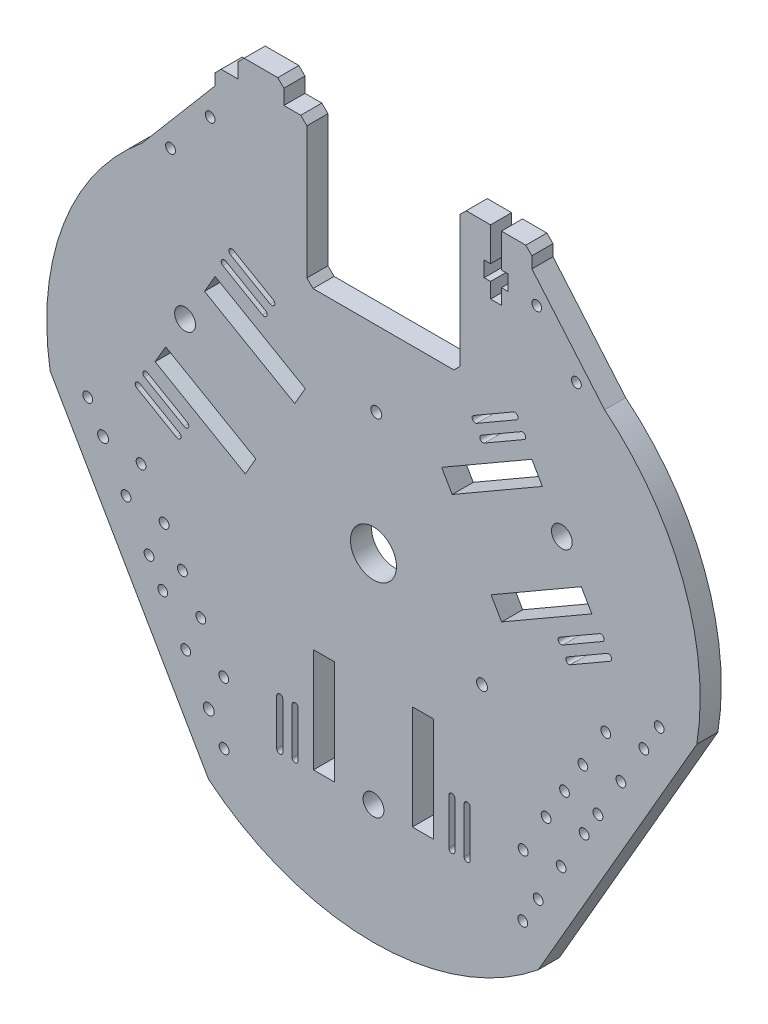
SolidWorks part; units mm, degrees
ref_plane "Front Plane" through (0, 0, 0) normal (0, 0, 1) x (1, 0, 0)
ref_plane "Top Plane" through (0, 0, 0) normal (0, 1, 0) x (1, 0, 0)
ref_plane "Right Plane" through (0, 0, 0) normal (1, 0, 0) x (0, 0, -1)
sketch "Sketch1" plane through (0, 0, 0) normal (0, 0, 1) x (1, 0, 0)
  circle A0 centre (0, 0) radius 110
  dimension "D1" = 220
extrude "Boss-Extrude1" add sketch "Sketch1" along normal blind 6.88
sketch "Sketch2" plane through (0, 0, 6.88) normal (0, 0, 1) x (1, 0, 0)
  line L0 (-105.5392, -1.2008) -> (-53.8095, -90.7992)
  line L1 (53.8095, -90.7992) -> (105.5392, -1.2008)
  line L2 (51.7297, 92) -> (-51.7297, 92)
  line L3 (-21.6506, 12.5) -> (21.6506, 12.5)
  line L4 (21.6506, 12.5) -> (0, -25)
  line L5 (0, -25) -> (-21.6506, 12.5)
  line L6 (0, 12.5) -> (0, 0) construction
  line L7 (0, 0) -> (-10.8253, -6.25) construction
  line L8 (10.8253, -6.25) -> (0, 0) construction
  arc A0 (-53.8095, -90.7992) -> (53.8095, -90.7992) centre (0, -25) ccw
  arc A1 (105.5392, -1.2008) -> (51.7297, 92) centre (21.6506, 12.5) ccw
  arc A2 (-51.7297, 92) -> (-105.5392, -1.2008) centre (-21.6506, 12.5) ccw
  circle A3 centre (0, 0) radius 250
  circle A4 centre (0, 0) radius 110
  circle M1 centre (0, 0) radius 110
  dimension "D3" = 220
  dimension "D4" = 500
  dimension "D5" = 85
  dimension "D1" = 92
extrude "Cut-Extrude1" cut sketch "Sketch2" against normal through all contours A3 M1 | A2 L2 A1 M1 | A2 A0 L0 M1 | A1 L1 A0 M1 region at (-84.8334, -48.9786, 6.88) region at (0, 97.9571, 6.88) region at (84.8334, -48.9786, 6.88) region at (-242.9289, 0, 6.88)
sketch "Sketch3" plane through (0, 0, 6.88) normal (0, 0, 1) x (1, 0, 0)
  line L0 (0, 0) -> (-95.2628, 55) construction
  line L1 (0, 0) -> (95.2628, 55) construction
  line L2 (0, 0) -> (0, -110) construction
  arc A0 (-51.7297, 92) -> (-105.5392, -1.2008) centre (-21.6506, 12.5) ccw construction
  arc A1 (105.5392, -1.2008) -> (51.7297, 92) centre (21.6506, 12.5) ccw construction
  arc A2 (-53.8095, -90.7992) -> (53.8095, -90.7992) centre (0, -25) ccw construction
sketch "Sketch4" plane through (0, 0, 0) normal (0, 0, -1) x (-1, 0, 0)
  line L0 (41.8329, 1.5432) -> (38.3929, 7.5015) construction
  line L1 (25.6929, 29.4985) -> (22.2529, 35.4568) construction
  line L2 (55.1378, 46.4985) -> (51.6978, 52.4568) construction
  line L3 (71.2778, 18.5432) -> (67.8378, 24.5015) construction
  line L4 (41.8329, 1.5432) -> (38.3929, 7.5015)
  line L5 (25.6929, 29.4985) -> (22.2529, 35.4568)
  line L6 (55.1378, 46.4985) -> (51.6978, 52.4568)
  line L7 (71.2778, 18.5432) -> (67.8378, 24.5015)
  line L8 (71.2778, 18.5432) -> (41.8329, 1.5432)
  line L9 (38.3929, 7.5015) -> (67.8378, 24.5015)
  line L10 (55.1378, 46.4985) -> (25.6929, 29.4985)
  line L11 (22.2529, 35.4568) -> (51.6978, 52.4568)
  line L12 (67.8378, 24.5015) -> (55.1378, 46.4985) construction
  line L13 (38.3929, 7.5015) -> (25.6929, 29.4985) construction
  line L14 (61.4878, 35.5) -> (32.0429, 18.5) construction
  circle A0 centre (32.0429, 18.5) radius 3.4 construction
  circle A1 centre (61.4878, 35.5) radius 3.4
  dimension "D1" = 6.8
extrude "Cut-Extrude2" cut sketch "Sketch4" against normal blind 10
ref_axis "Axis1" through (0, 0, -0.344) along (0, 0, 1)
pattern_circular "CirPattern1" count 3 over 360 about axis through (0, 0, -0.344) along (0, 0, 1) of "Cut-Extrude2"
sketch "Sketch6" plane through (0, 0, 6.88) normal (0, 0, 1) x (1, 0, 0)
  line L0 (-21.7297, 112) -> (-21.7297, 97)
  line L1 (51.7297, 92) -> (-51.7297, 92)
  line L2 (51.7297, 92) -> (51.7297, 112)
  line L3 (51.7297, 112) -> (28.2703, 112)
  line L4 (-51.7297, 92) -> (-51.7297, 112)
  line L5 (-21.7297, 97) -> (28.2703, 97)
  line L6 (28.2703, 97) -> (28.2703, 112)
  line L7 (-21.7297, 112) -> (-51.7297, 112)
  dimension "D1" = 20
  dimension "D2" = 15
  dimension "D3" = 50
  dimension "D4" = 30
extrude "Boss-Extrude2" add sketch "Sketch6" against normal up to vertex (6.88 mm away) up to point (51.7297, 92, 0)
chamfer "Chamfer1" distance 21 angle 45 2 edges at (-51.7297, 92, 3.44) (51.7297, 92, 3.44) first distance on face at (-51.7297, 102, 3.44) first distance on face at (51.7297, 102, 3.44)
sketch "Sketch7" plane through (0, 0, 6.88) normal (0, 0, 1) x (1, 0, 0)
  line L0 (-21.7297, 112) -> (-51.7297, 112) construction
  line L1 (-21.7297, 97) -> (28.2703, 97)
  line L2 (-21.7297, 97) -> (-21.7297, 65)
  line L3 (-21.7297, 65) -> (28.2703, 65)
  line L4 (28.2703, 97) -> (28.2703, 65)
  line L5 (28.2703, 112) -> (28.2703, 97) construction
  dimension "D1" = 47
extrude "Cut-Extrude5" cut sketch "Sketch7" against normal through all
sketch "Sketch8" plane through (0, 0, 6.88) normal (0, 0, 1) x (1, 0, 0)
  line L0 (51.7297, 112) -> (28.2703, 112) construction
  line L5 (41.775, 133) -> (38.225, 133)
  line L6 (41.775, 133) -> (41.775, 91)
  line L7 (41.775, 91) -> (38.225, 91)
  line L8 (38.225, 133) -> (38.225, 91)
  line L9 (41.775, 133) -> (38.225, 91) construction
  line L10 (41.775, 91) -> (38.225, 133) construction
  line L12 (43.86, 96) -> (36.14, 96)
  line L13 (43.86, 96) -> (43.86, 101)
  line L14 (43.86, 101) -> (36.14, 101)
  line L15 (36.14, 96) -> (36.14, 101)
  line L16 (43.86, 96) -> (36.14, 101) construction
  line L17 (43.86, 101) -> (36.14, 96) construction
  point P0 (40, 112)
  point P7 (40, 98.5)
  dimension "D1" = 3.55
  dimension "D2" = 21
  dimension "D3" = 7.72
  dimension "D4" = 5
  dimension "D5" = 11
extrude "Cut-Extrude6" cut sketch "Sketch8" against normal blind 6.88 contours L13 L14 L6 L12 | L6 L12 L8 L7 | L6 L14 L8 L12 | L15 L12 L8 L14 | L14 L6 L8 region at (40, 117, 6.88) region at (42.8175, 98.5, 6.88) region at (40, 98.5, 6.88) region at (37.1825, 98.5, 6.88) region at (40, 93.5, 6.88)
sketch "Sketch9" plane through (0, 0, 6.88) normal (0, 0, 1) x (1, 0, 0)
  line L0 (-21.7297, 112) -> (-51.7297, 112) construction
  line L1 (-29.2297, 105.12) -> (-44.2297, 105.12)
  line L2 (-29.2297, 105.12) -> (-29.2297, 118.88)
  line L3 (-29.2297, 118.88) -> (-44.2297, 118.88)
  line L4 (-44.2297, 105.12) -> (-44.2297, 118.88)
  line L5 (-29.2297, 105.12) -> (-44.2297, 118.88) construction
  line L6 (-29.2297, 118.88) -> (-44.2297, 105.12) construction
  point P0 (-36.7297, 112)
  dimension "D1" = 15
  dimension "D2" = 6.88
extrude "Boss-Extrude3" add sketch "Sketch9" against normal up to vertex (6.88 mm away) up to point (-21.7297, 112, 0)
sketch "Sketch10" plane through (0, 0, 6.88) normal (0, 0, 1) x (1, 0, 0)
  line L2 (19.58, -109) -> (19.58, -71) construction
  line L4 (25.58, -71) -> (25.58, -56) construction
  line L5 (24.58, -71) -> (24.58, -56)
  line L6 (26.58, -71) -> (26.58, -56)
  line L7 (25.58, -63.5) -> (30.58, -63.5) construction
  line L8 (28.08, -63.5) -> (28.08, -58.2067) construction
  line L9 (19.58, -71) -> (19.58, -37) construction
  line L10 (30.58, -71) -> (30.58, -56) construction
  line L11 (31.58, -71) -> (31.58, -56)
  line L12 (29.58, -71) -> (29.58, -56)
  line L15 (-25.58, -71) -> (-25.58, -56) construction
  line L16 (-24.58, -71) -> (-24.58, -56)
  line L17 (-26.58, -71) -> (-26.58, -56)
  line L18 (-30.58, -71) -> (-30.58, -56) construction
  line L19 (-31.58, -71) -> (-31.58, -56)
  line L20 (-29.58, -71) -> (-29.58, -56)
  line L21 (-28.08, -63.5) -> (-28.08, -58.2067) construction
  line L22 (-25.58, -63.5) -> (-30.58, -63.5) construction
  arc A0 (24.58, -71) -> (26.58, -71) centre (25.58, -71) ccw
  arc A1 (26.58, -56) -> (24.58, -56) centre (25.58, -56) ccw
  arc A2 (31.58, -71) -> (29.58, -71) centre (30.58, -71) cw
  arc A3 (29.58, -56) -> (31.58, -56) centre (30.58, -56) cw
  arc A4 (-24.58, -71) -> (-26.58, -71) centre (-25.58, -71) cw
  arc A5 (-26.58, -56) -> (-24.58, -56) centre (-25.58, -56) cw
  arc A6 (-31.58, -71) -> (-29.58, -71) centre (-30.58, -71) ccw
  arc A7 (-29.58, -56) -> (-31.58, -56) centre (-30.58, -56) ccw
  point P6 (25.58, -63.5)
  point P21 (30.58, -63.5)
  point P30 (-25.58, -63.5)
  point P37 (-30.58, -63.5)
  dimension "D1" = 2
  dimension "D2" = 15
  dimension "D3" = 5
  dimension "D4" = 1.5
extrude "Cut-Extrude7" cut sketch "Sketch10" against normal blind 6.88
pattern_circular "CirPattern2" count 3 over 360 about axis through (0, 0, -0.344) along (0, 0, 1) of "Cut-Extrude7"
sketch "Sketch11" plane through (0, 0, 0) normal (0, 0, -1) x (-1, 0, 0)
  line L0 (-0.9365, 40.3779) -> (-35.4365, -19.3779) construction
  line L1 (-35.4365, -19.3779) -> (53.7641, -70.8779) construction
  line L2 (53.7641, -70.8779) -> (88.2641, -11.1221) construction
  line L3 (88.2641, -11.1221) -> (-0.9365, 40.3779) construction
  line L4 (71.0141, -41) -> (79.6743, -46) construction
  line L5 (105.5392, -1.2008) -> (53.8095, -90.7992) construction
  circle A4 centre (-0.9365, 40.3779) radius 1.775
  circle A5 centre (-35.4365, -19.3779) radius 1.775
  circle A6 centre (88.2641, -11.1221) radius 1.775
  circle A7 centre (53.7641, -70.8779) radius 1.775
  dimension "D4" = 3.55
  dimension "D1" = 69
  dimension "D2" = 103
  dimension "D3" = 10
extrude "Cut-Extrude8" cut sketch "Sketch11" against normal blind 10
chamfer "Chamfer2" distance 2 angle 45 8 edges at (28.2703, 65, 3.44) (-21.7297, 65, 3.44) (28.2703, 112, 3.44) (51.7297, 112, 3.44) (-51.7297, 112, 3.44) (-44.2297, 118.88, 3.44) (-29.2297, 118.88, 3.44) (-21.7297, 112, 3.44)
sketch "Sketch13" plane through (0, 0, 0) normal (0, 0, -1) x (-1, 0, 0)
  circle A0 centre (0, 0) radius 7.5
  dimension "D1" = 15
extrude "Cut-Extrude10" cut sketch "Sketch13" against normal blind 10
sketch "Sketch15" plane through (0, 0, 0) normal (0, 0, -1) x (-1, 0, 0)
  line L1 (0, 0) -> (0, -110) construction
  line L2 (-34.5, 82) -> (-19.5, 82) construction
  line L3 (-27, 82) -> (-27, 72) construction
  line L4 (0, 92) -> (0, 117.1571) construction
  line L5 (27, 82) -> (27, 72) construction
  line L6 (34.5, 82) -> (19.5, 82) construction
  line L7 (-34.5, 82) -> (-44.5, 82) construction
  circle A0 centre (-34.5, 82) radius 1.6 construction
  circle A1 centre (-27, 72) radius 1.6 construction
  circle A2 centre (-19.5, 82) radius 1.6 construction
  circle A3 centre (-4.5, 82) radius 1.6 construction
  circle A4 centre (-12, 72) radius 1.6 construction
  circle A5 centre (0, 82) radius 1.6 construction
  circle A6 centre (0, 72) radius 1.6 construction
  circle A7 centre (12, 72) radius 1.6 construction
  circle A8 centre (4.5, 82) radius 1.6 construction
  circle A9 centre (19.5, 82) radius 1.6 construction
  circle A10 centre (27, 72) radius 1.6 construction
  circle A11 centre (34.5, 82) radius 1.6 construction
  circle A34 centre (53.7641, -70.8779) radius 1.6
  circle A35 centre (48.8538, -59.3827) radius 1.6
  circle A36 centre (61.2641, -57.8875) radius 1.6
  circle A37 centre (56.3538, -46.3923) radius 1.6
  circle A38 centre (68.7641, -44.8971) radius 1.6
  circle A39 centre (62.3538, -36) radius 1.6
  circle A40 centre (73.2641, -37.1029) radius 1.6
  circle A41 centre (68.3538, -25.6077) radius 1.6
  circle A42 centre (80.7641, -24.1125) radius 1.6
  circle A43 centre (75.8538, -12.6173) radius 1.6
  circle A44 centre (88.2641, -11.1221) radius 1.6
  circle A45 centre (-88.2641, -11.1221) radius 1.6
  circle A46 centre (-75.8538, -12.6173) radius 1.6
  circle A47 centre (-80.7641, -24.1125) radius 1.6
  circle A48 centre (-68.3538, -25.6077) radius 1.6
  circle A49 centre (-73.2641, -37.1029) radius 1.6
  circle A50 centre (-62.3538, -36) radius 1.6
  circle A51 centre (-68.7641, -44.8971) radius 1.6
  circle A52 centre (-56.3538, -46.3923) radius 1.6
  circle A53 centre (-61.2641, -57.8875) radius 1.6
  circle A54 centre (-48.8538, -59.3827) radius 1.6
  circle A55 centre (-53.7641, -70.8779) radius 1.6
  circle A56 centre (-44.5, 82) radius 1.6 construction
  circle A57 centre (44.5, 82) radius 1.6 construction
  circle A58 centre (93.2641, -2.4619) radius 1.6
  circle A59 centre (48.7641, -79.5381) radius 1.6
  circle A60 centre (-48.7641, -79.5381) radius 1.6
  circle A61 centre (-93.2641, -2.4619) radius 1.6
  point P78 (0, 0)
  point P80 (0, 0)
  point P92 (0, 0)
  dimension "D2" = 3.2
  dimension "D1" = 82
  dimension "D3" = 34.5
  dimension "D4" = 15
  dimension "D5" = 10
  dimension "D6" = 15
  dimension "D7" = 15
  dimension "D8" = 3
  dimension "D9" = 10
  dimension "D10" = 3
extrude "Cut-Extrude11" cut sketch "Sketch15" against normal blind 10
sketch "Sketch16" [suppressed] plane through (0, 0, 0) normal (0, 0, -1) x (-1, 0, 0)
  line L0 (0, 0) -> (-95.2628, 55) construction
  line L1 (0, 0) -> (-95.2628, 55) construction
  circle A0 centre (-48.7641, -79.5381) radius 1.6 construction
  circle A1 centre (-53.7641, -70.8779) radius 1.6 construction
  circle A2 centre (-68.7641, -44.8971) radius 1.6 construction
  circle A3 centre (-61.2641, -57.8875) radius 1.6 construction
  circle A4 centre (-48.8538, -59.3827) radius 1.6 construction
  circle A5 centre (-56.3538, -46.3923) radius 1.6 construction
  circle A6 centre (-73.2641, -37.1029) radius 1.6 construction
  circle A7 centre (-62.3538, -36) radius 1.6 construction
  circle A8 centre (-68.3538, -25.6077) radius 1.6 construction
  circle A9 centre (-80.7641, -24.1125) radius 1.6 construction
  circle A10 centre (-75.8538, -12.6173) radius 1.6 construction
  circle A11 centre (-88.2641, -11.1221) radius 1.6 construction
  circle A12 centre (-93.2641, -2.4619) radius 1.6 construction
  circle A13 centre (-48.7641, -79.5381) radius 1.6 construction
  circle A14 centre (-53.7641, -70.8779) radius 1.6 construction
  circle A15 centre (-68.7641, -44.8971) radius 1.6 construction
  circle A16 centre (-61.2641, -57.8875) radius 1.6 construction
  circle A17 centre (-48.8538, -59.3827) radius 1.6 construction
  circle A18 centre (-56.3538, -46.3923) radius 1.6 construction
  circle A19 centre (-73.2641, -37.1029) radius 1.6 construction
  circle A20 centre (-62.3538, -36) radius 1.6 construction
  circle A21 centre (-68.3538, -25.6077) radius 1.6 construction
  circle A22 centre (-80.7641, -24.1125) radius 1.6 construction
  circle A23 centre (-75.8538, -12.6173) radius 1.6 construction
  circle A24 centre (-88.2641, -11.1221) radius 1.6 construction
  circle A25 centre (-93.2641, -2.4619) radius 1.6 construction
  circle A26 centre (-44.5, 82) radius 1.6
  circle A27 centre (-34.5, 82) radius 1.6
  circle A28 centre (-27, 72) radius 1.6
  circle A29 centre (-19.5, 82) radius 1.6
  circle A30 centre (-12, 72) radius 1.6
  circle A31 centre (0, 72) radius 1.6
  circle A32 centre (-4.5, 82) radius 1.6
  circle A33 centre (12, 72) radius 1.6
  circle A34 centre (27, 72) radius 1.6
  circle A35 centre (19.5, 82) radius 1.6
  circle A36 centre (4.5, 82) radius 1.6
  circle A37 centre (34.5, 82) radius 1.6
  circle A38 centre (44.5, 82) radius 1.6
extrude "Cut-Extrude12" [suppressed] cut sketch "Sketch16" against normal through all
sketch "Sketch17" plane through (0, 0, 0) normal (0, 0, -1) x (-1, 0, 0)
  line L0 (-53.3032, 96.6968) -> (-66.2356, 81.4405) construction
  line L2 (-51.7297, 106.2855) -> (-75.4371, 78.318) construction
  line L3 (-63.5834, 92.3018) -> (-59.7694, 89.0687) construction
  line L4 (0, 0) -> (0, 141.0352) construction
  line L5 (63.5834, 92.3018) -> (59.7694, 89.0687) construction
  line L6 (53.3032, 96.6968) -> (66.2356, 81.4405) construction
  circle A0 centre (-53.3032, 96.6968) radius 1.6
  circle A1 centre (-66.2356, 81.4405) radius 1.6
  circle A2 centre (66.2356, 81.4405) radius 1.6
  circle A3 centre (53.3032, 96.6968) radius 1.6
  dimension "D1" = 3.2
  dimension "D2" = 5
  dimension "D3" = 20
extrude "Cut-Extrude13" cut sketch "Sketch17" against normal through all
